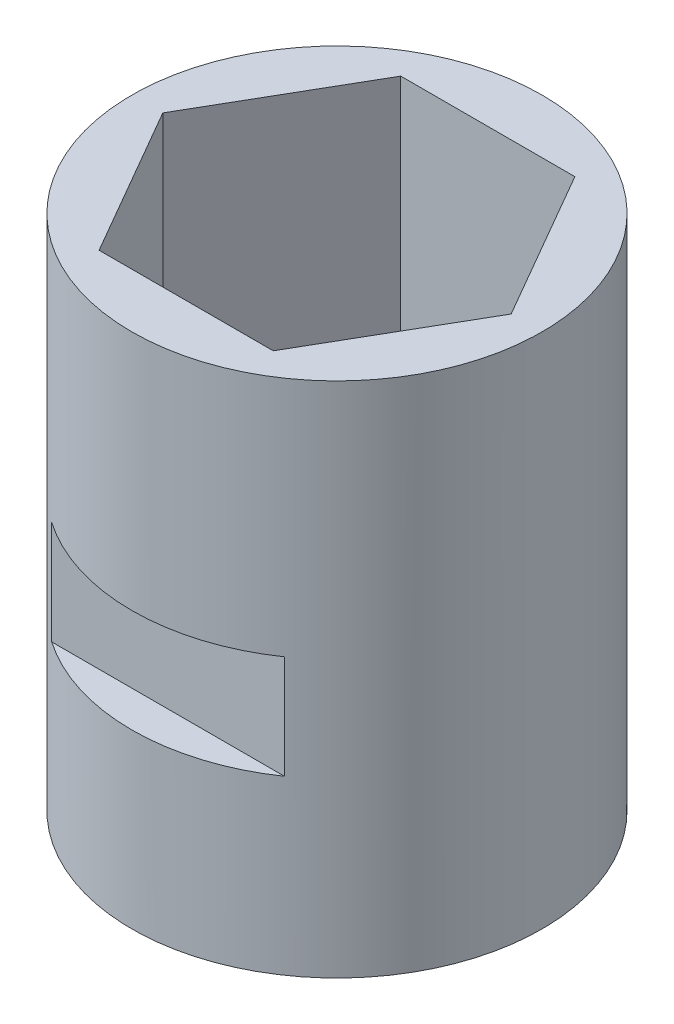
SolidWorks part; units mm, degrees
material "Polyester Resin"
ref_plane "Front Plane" through (0, 0, 0) normal (0, 0, 1) x (1, 0, 0)
ref_plane "Top Plane" through (0, 0, 0) normal (0, 1, 0) x (1, 0, 0)
ref_plane "Right Plane" through (0, 0, 0) normal (1, 0, 0) x (0, 0, -1)
sketch "Sketch1" plane through (0, 0, 0) normal (0, 1, 0) x (1, 0, 0)
  line L1 (-3.2079, 5.5563) -> (-6.4158, 0)
  line L2 (-6.4158, 0) -> (-3.2079, -5.5562)
  line L3 (-3.2079, -5.5562) -> (3.2079, -5.5562)
  line L4 (3.2079, -5.5562) -> (6.4158, 0)
  line L5 (6.4158, 0) -> (3.2079, 5.5563)
  line L6 (3.2079, 5.5563) -> (-3.2079, 5.5563)
  circle A0 centre (0, 0) radius 5.5562 construction
  circle A1 centre (0, 0) radius 7.5565
  dimension "D2" = 15.113
  dimension "D1" = 11.1125
extrude "Boss-Extrude1" add sketch "Sketch1" along normal blind 15.875
sketch "Sketch2" plane through (0, 0, 0) normal (0, -1, 0) x (1, 0, 0)
  circle A0 centre (0, 0) radius 7.5565
  circle A1 centre (0, 0) radius 3.3782
  dimension "D1" = 6.7564
extrude "Boss-Extrude2" add sketch "Sketch2" along normal blind 3.175
sketch "Sketch3" plane through (0, 0, 0) normal (1, 0, 0) x (0, 0, -1)
  line L0 (-6.223, 6.985) -> (-6.223, 3.175)
  line L1 (6.223, 6.985) -> (6.223, 3.175)
  line L2 (-7.5565, -3.175) -> (7.5565, -3.175) construction
  line L3 (-6.223, 6.985) -> (-8.202, 6.985)
  line L4 (-8.202, 6.985) -> (-8.202, 3.175)
  line L5 (-8.202, 3.175) -> (-6.223, 3.175)
  line L6 (6.223, 6.985) -> (8.4791, 6.985)
  line L7 (8.4791, 6.985) -> (8.4791, 3.175)
  line L8 (8.4791, 3.175) -> (6.223, 3.175)
  dimension "D1" = 12.446
  dimension "D2" = 6.223
  dimension "D3" = 3.81
  dimension "D4" = 3.81
  dimension "D5" = 6.35
  dimension "D6" = 6.35
extrude "Cut-Extrude1" cut sketch "Sketch3" against normal through all and the other way through all
equation "\"AB_Central_Bushing_Length\" = .75in"
equation "\"Solid_Length\"= .125in"
equation "\"Hex_Length\"= \"AB_Central_Bushing_Length\" - \"Solid_Length\""
equation "\"D1@Boss-Extrude1\"=\"Hex_Length\""
equation "\"D1@Boss-Extrude2\"=\"Solid_Length\""
equation "\"Cutout_Angle\" = 80"
